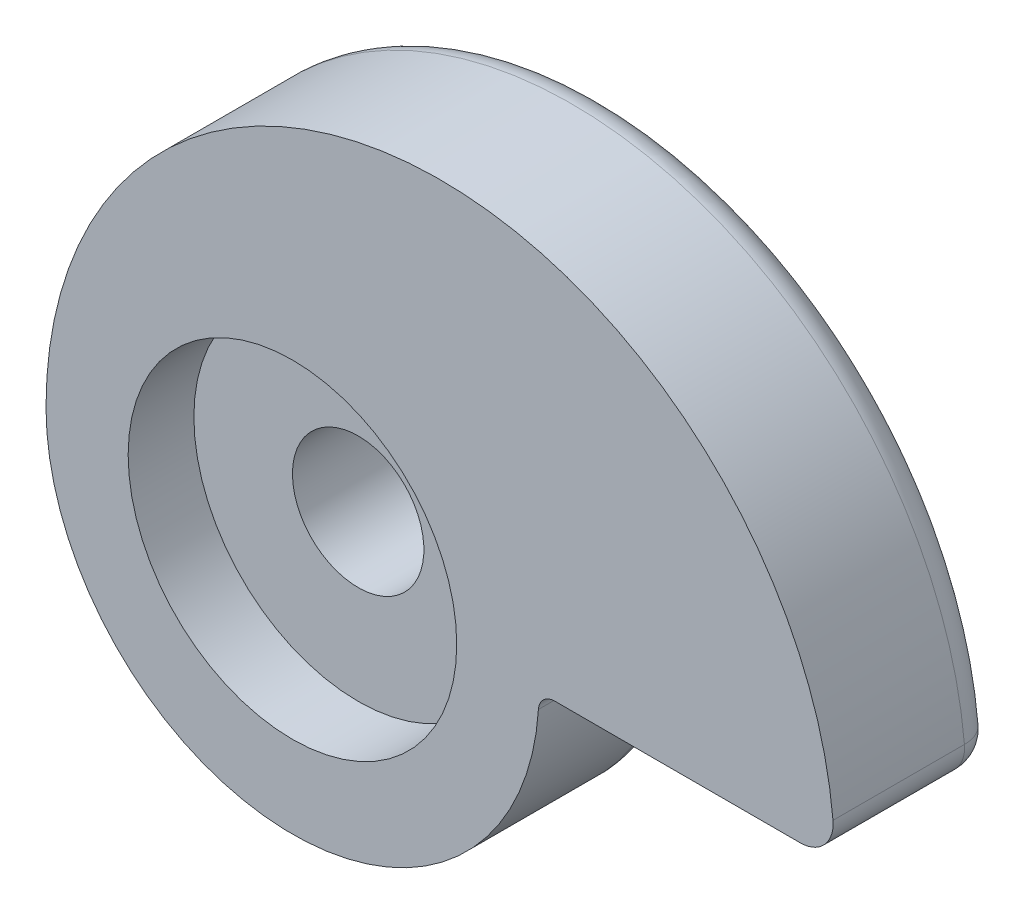
SolidWorks part; units mm, degrees
ref_plane "Front Plane" through (0, 0, 0) normal (0, 0, 1) x (1, 0, 0)
ref_plane "Top Plane" through (0, 0, 0) normal (0, 1, 0) x (1, 0, 0)
ref_plane "Right Plane" through (0, 0, 0) normal (1, 0, 0) x (0, 0, -1)
sketch "Sketch1" plane through (0, 0, 0) normal (0, 0, 1) x (1, 0, 0)
  line L0 (-12, 0) -> (12, 0) construction
  line L2 (3, 0) -> (12, 0)
  arc A0 (12, 0) -> (-12, 0) centre (0, 0) ccw
  circle A3 centre (-4.5, 0) radius 2
  arc A4 (-12, 0) -> (3, 0) centre (-4.5, 0) ccw
  dimension "D1" = 24
  dimension "D2" = 4
  dimension "D3" = 7.5
extrude "Boss-Extrude1" add sketch "Sketch1" along normal blind 5
sketch "Sketch3" plane through (0, 0, 0) normal (0, 0, 1) x (1, 0, 0)
  circle A0 centre (-4.5, 0) radius 5
  circle A1 centre (-4.5, 0) radius 2 construction
  circle A2 centre (-4.5, 0) radius 2
  dimension "D1" = 10
extrude "Boss-Extrude2" add sketch "Sketch3" against normal blind 5
sketch "Sketch4" plane through (0, 0, -5) normal (0, 0, -1) x (-1, 0, 0)
  line L1 (-2.0014, -1) -> (11.0014, -1)
  line L2 (-2.0014, -1) -> (-2.0014, 1)
  line L3 (-2.0014, 1) -> (11.0014, 1)
  line L4 (11.0014, -1) -> (11.0014, 1)
  line L5 (-2.0014, -1) -> (11.0014, 1) construction
  line L6 (-2.0014, 1) -> (11.0014, -1) construction
  point P0 (4.5, 0)
  dimension "D1" = 2
extrude "Cut-Extrude1" cut sketch "Sketch4" against normal blind 3
fillet "Fillet1" radius 1 4 edges at (-7.8155, 1, -2) (-7.8155, -1, -2) (-1.1845, -1, -2) (-1.1845, 1, -2)
sketch "Sketch5" plane through (0, 0, 5) normal (0, 0, -1) x (-1, 0, 0)
  circle A1 centre (4.5, 0) radius 5
  circle A2 centre (4.5, 0) radius 2 construction
  dimension "D1" = 10
extrude "Cut-Extrude2" cut sketch "Sketch5" along normal blind 2
fillet "Fillet2" radius 1.5 1 edges at (0.5, 0, 0)
fillet "Fillet3" radius 1 1 edges at (12, 0, 2.5)
fillet "Fillet4" radius 0.5 19 edges at (3, 0, 2.5) (-2.7679, 1, -4) (-2.6741, 0.8161, -2.4221) (-2.5871, -0.5836, -2.188) (-6.2321, 1, -4) (-6.4129, 0.5836, -2.188) (-6.3259, -0.8161, -2.4221) (-9.399, 1, -4) (-9.4377, 0.7866, -2.3825) (0.399, 1, -4) (0.4617, 0.6177, -2.2136) (-1.1845, -1, -5) (0.399, -1, -4) (-2.7679, -1, -4) (-7.8155, -1, -5) (-6.2321, -1, -4) (-9.399, -1, -4) (-9.4617, -0.6177, -2.2136) (0.4377, -0.7866, -2.3825)
fillet "Fillet5" radius 1 5 edges at (-0.546, 11.9876, 0) (11.693, 0.3258, 0) (7.2194, 0, 0) (3.142, -0.1356, 0) (-4.7345, -7.4963, 0)
